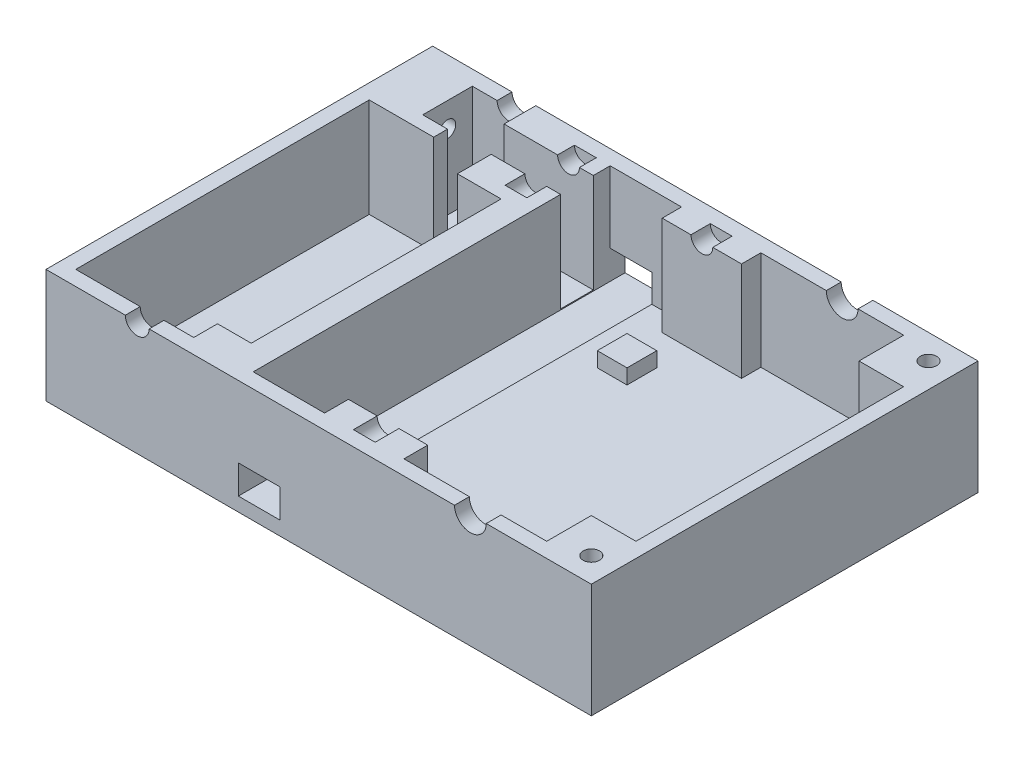
SolidWorks part; units mm, degrees
ref_plane "前视基准面" through (0, 0, 0) normal (0, 0, 1) x (1, 0, 0)
ref_plane "上视基准面" through (0, 0, 0) normal (0, 1, 0) x (1, 0, 0)
ref_plane "右视基准面" through (0, 0, 0) normal (1, 0, 0) x (0, 0, -1)
other "Configuration Table"
sketch "草图1" plane through (0, 0, 0) normal (0, 1, 0) x (1, 0, 0)
  line L1 (-27.5, 19.5) -> (27.5, 19.5)
  line L2 (-27.5, 19.5) -> (-27.5, -19.5)
  line L3 (-27.5, -19.5) -> (27.5, -19.5)
  line L4 (27.5, 19.5) -> (27.5, -19.5)
  line L5 (-27.5, 19.5) -> (27.5, -19.5) construction
  line L6 (-27.5, -19.5) -> (27.5, 19.5) construction
  point P0 (0, 0)
  dimension "D1" = 55
  dimension "D2" = 39
extrude "凸台-拉伸1" add sketch "草图1" along normal blind 11.5
shell "抽壳1" thickness 1.5 removed face at (0, 11.5, 0)
sketch "草图2" plane through (0, 0, -19.5) normal (0, 0, -1) x (-1, 0, 0)
  line L0 (7.9, 1.6) -> (4.1, 1.6) construction
  line L1 (3.9, 4.3) -> (8.1, 4.3)
  line L2 (3.9, 4.3) -> (3.9, 1.4)
  line L3 (3.9, 1.4) -> (8.1, 1.4)
  line L4 (8.1, 4.3) -> (8.1, 1.4)
  line L5 (7.9, 1.6) -> (7.9, 4.1) construction
  line L6 (7.9, 4.1) -> (4.1, 4.1) construction
  line L7 (4.1, 1.6) -> (4.1, 4.1) construction
  circle A0 centre (-15.3, 11.5) radius 1.6
  circle A1 centre (18.3, 11.5) radius 1.2
  circle A2 centre (-15.3, 11.5) radius 1.5 construction
  circle A3 centre (18.3, 11.5) radius 1 construction
  dimension "D1" = 0.1
  dimension "D2" = 0.2
  dimension "D3" = 0.2
  dimension "D4" = 0.2
  dimension "D5" = 0.2
  dimension "D6" = 0.2
extrude "切除-拉伸1" cut sketch "草图2" against normal through all
sketch "草图3" plane through (0, 1.5, 0) normal (0, 1, 0) x (1, 0, 0)
  line L0 (-25.8, -15.5) -> (-10.8, -15.5) construction
  line L5 (-10.7, 9.6) -> (-10.7, -15.6)
  line L6 (-15.1, 13) -> (-8.1, 13)
  line L7 (-15.1, 13) -> (-15.1, 9.6)
  line L8 (-15.1, 9.6) -> (-10.7, 9.6)
  line L10 (-17.1, -18) -> (13.7, -18) construction
  line L11 (-10.7, -18) -> (-8.1, -18)
  line L13 (-14.3, -17.8) -> (-14.3, -15.5) construction
  line L16 (-15.3, 9.5) -> (-15.3, 11.5) construction
  line L17 (-10.8, 9.5) -> (-10.8, -15.5) construction
  line L18 (-8.1, 18) -> (-8.1, -18) construction
  line L19 (13.7, 18) -> (-17.1, 18) construction
  line L20 (-17.1, 18) -> (-8.1, 18)
  line L21 (-17.1, 18) -> (-17.1, 16.3)
  line L22 (-17.1, 16.3) -> (-8.1, 16.3)
  line L23 (-8.1, 18) -> (-8.1, 16.3)
  line L24 (-17.1, 18) -> (-17.1, 19.5) construction
  line L25 (-8.1, 13) -> (-8.1, -18)
  line L26 (4.6159, 15.85) -> (4.2435, 15.85) construction
  line L27 (-0.9, 18) -> (7.1, 18)
  line L28 (-0.9, 18) -> (-0.9, 16.05)
  line L29 (-0.9, 16.05) -> (7.1, 16.05)
  line L30 (7.1, 18) -> (7.1, 16.05)
  line L31 (4.1, -18.1452) -> (4.1, 18.1548) construction
  line L32 (-17.1, -18) -> (13.7, -18) construction
  line L33 (-0.9, -15.6) -> (7.1, -15.6)
  line L34 (-0.9, -15.6) -> (-0.9, -18)
  line L35 (-0.9, -18) -> (7.1, -18)
  line L36 (7.1, -15.6) -> (7.1, -18)
  line L38 (26, 18) -> (16.9, 18) construction
  line L39 (21.5, 18) -> (26, 18)
  line L40 (21.5, 18) -> (21.5, 13.5)
  line L41 (21.5, 13.5) -> (26, 13.5)
  line L42 (26, 18) -> (26, 13.5)
  line L43 (26, -18) -> (26, 18) construction
  line L44 (-26, 18) -> (-26, -18) construction
  line L45 (21.5, -13.5) -> (26, -13.5)
  line L46 (21.5, -13.5) -> (21.5, -18)
  line L47 (21.5, -18) -> (26, -18)
  line L48 (26, -13.5) -> (26, -18)
  line L49 (-26, 18) -> (-22, 18)
  line L50 (-26, 18) -> (-26, 13)
  line L52 (-22, 18) -> (-22, 13)
  line L53 (-26, 11.6) -> (-19.5, 11.6)
  line L54 (-26, 11.6) -> (-26, 13)
  line L55 (-22, 13) -> (-19.5, 13)
  line L56 (-19.5, 11.6) -> (-19.5, 13)
  line L57 (-15.3, 11.5) -> (-21.3, 11.5) construction
  line L58 (-19.3, 19) -> (-19.3, 11.5) construction
  line L59 (-10.8, 9.5) -> (-25.8, 9.5) construction
  line L60 (-19.5, 18) -> (-26, 18) construction
  line L62 (-14.1, -15.6) -> (-10.7, -15.6)
  line L63 (-14.1, -15.6) -> (-14.1, -18)
  line L64 (-14.1, -18) -> (-10.7, -18)
  dimension "D2" = 4
  dimension "D3" = 0.1
  dimension "D4" = 0.2
  dimension "D5" = 1.7
  dimension "D6" = 0.1
  dimension "D7" = 8
  dimension "D8" = 0.2
  dimension "D9" = 3
  dimension "D10" = 8
  dimension "D11" = 3
  dimension "D12" = 2.4
  dimension "D13" = 4.5
  dimension "D14" = 4.5
  dimension "D15" = 4.5
  dimension "D16" = 4.5
  dimension "D17" = 0.2
  dimension "D18" = 0.1
  dimension "D19" = 5
  dimension "D20" = 0.1
  dimension "D21" = 0.2
extrude "凸台-拉伸2" add sketch "草图3" along normal up to surface (10 mm away) up to face at (-23.125, 11.5, 0)
sketch "草图4" plane through (0, 0, 19.5) normal (0, 0, 1) x (1, 0, 0)
  circle A0 centre (3.1, 11.5) radius 1.1
  circle A1 centre (3.1, 11.5) radius 1 construction
  dimension "D1" = 0.1
extrude "切除-拉伸2" cut sketch "草图4" against normal offset from surface (36 mm away) 1.5 from offset 1.5 up to face at (-6, 2.85, -19.5) offset against normal yes
sketch "草图5" plane through (0, 0, -19.5) normal (0, 0, -1) x (-1, 0, 0)
  circle A0 centre (10.6, 11.5) radius 1.1
  circle A1 centre (10.6, 11.5) radius 1 construction
  dimension "D1" = 0.1
extrude "切除-拉伸3" cut sketch "草图5" against normal blind 7 from offset 1.5 offset against normal yes
sketch "草图6" plane through (0, 1.5, 0) normal (0, 1, 0) x (1, 0, 0)
  line L0 (-0.9, 18) -> (-8.1, 18) construction
  line L1 (-1.1, 12.7) -> (1.9, 12.7)
  line L2 (-1.1, 12.7) -> (-1.1, 9.7)
  line L3 (-1.1, 9.7) -> (1.9, 9.7)
  line L4 (1.9, 12.7) -> (1.9, 9.7)
  line L6 (-8.1, -18) -> (-8.1, 13) construction
  line L8 (-32, 4) -> (-27.5, 4)
  line L9 (-32, 4) -> (-32, -4)
  line L10 (-32, -4) -> (-27.5, -4)
  line L11 (-27.5, 4) -> (-27.5, -4)
  line L14 (-27.5, 0) -> (-45.462, 0) construction
  line L15 (-27.5, 19.5) -> (-27.5, -19.5) construction
  dimension "D1" = 8.3
  dimension "D2" = 3
  dimension "D3" = 3
  dimension "D4" = 7
  dimension "D5" = 4.5
  dimension "D6" = 8
extrude "凸台-拉伸3" add sketch "草图6" along normal blind 1.5 and the other way blind 1.5
sketch "草图7" plane through (0, 0, 0) normal (0, -1, 0) x (1, 0, 0)
  line L0 (-32, -4) -> (-32, 4) construction
  line L1 (27.5, 0) -> (56.3628, 0) construction
  line L2 (27.5, 19.5) -> (27.5, -19.5) construction
  line L3 (21.5, 13.5) -> (21.5, 18) construction
  line L4 (26, 13.5) -> (21.5, 13.5) construction
  circle A0 centre (-29.8, 0) radius 1
  circle A1 centre (25, 17) radius 0.825
  circle A2 centre (25, -17) radius 0.825
  dimension "D1" = 2
  dimension "D2" = 2.2
  dimension "D3" = 1.65
  dimension "D4" = 3.5
  dimension "D5" = 3.5
extrude "切除-拉伸4" cut sketch "草图7" against normal through all
sketch "草图8" plane through (0, 1.5, 0) normal (0, 1, 0) x (1, 0, 0)
  line L0 (27.5, 0) -> (45.6897, 0) construction
  line L1 (27.5, -19.5) -> (27.5, 19.5) construction
  line L2 (26, -13.5) -> (26, 13.5) construction
  line L3 (26, -13.5) -> (21.5, -13.5) construction
  circle A0 centre (23, 7.6) radius 1
  circle A1 centre (23, -10.5) radius 1
  dimension "D1" = 2
  dimension "D2" = 3
  dimension "D3" = 3
  dimension "D4" = 2
  dimension "D5" = 3
  dimension "D6" = 3
extrude "切除-拉伸5" cut sketch "草图8" against normal through all
sketch "草图9" plane through (-27.5, 0, 0) normal (-1, 0, 0) x (0, 0, 1)
  line L0 (-19.5, 11.5) -> (19.5, 11.5) construction
  line L1 (-18, 11.5) -> (-18, 1.5) construction
  circle A0 centre (-15.502, 9) radius 0.825
  dimension "D1" = 1.65
  dimension "D2" = 2.5
  dimension "D3" = 2.498
extrude "切除-拉伸6" cut sketch "草图9" against normal up to next
